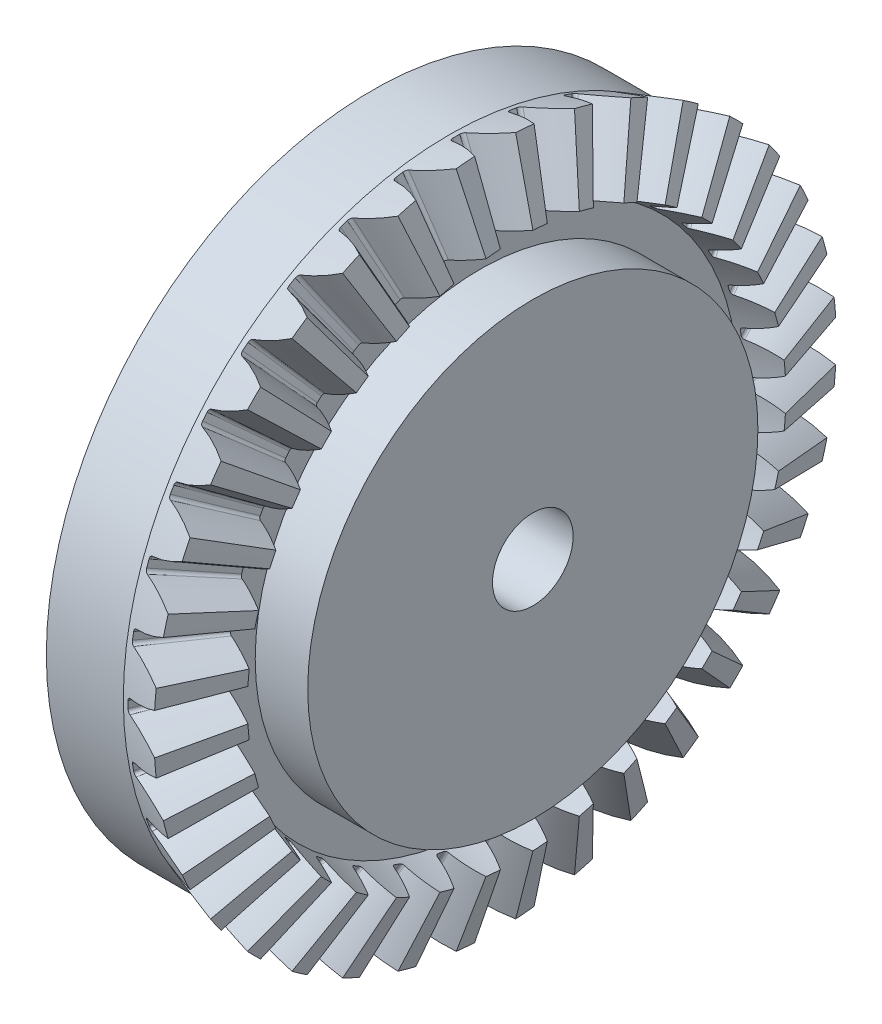
SolidWorks part; units mm, degrees
revolve "Base-Revolve" add sketch "BasProSke" angle 360 about L0
sketch "BasProSke" plane through (0, 0, 0) normal (0, 1, 0) x (1, 0, 0)
  line L0 (-10, 0) -> (60, 0) construction
  line L1 (0, 0) -> (0, 8.684)
  line L2 (0, 0) -> (0.8323, 0)
  line L3 (0.8323, 0) -> (0.8323, 6.8532)
  line L4 (3.948, 0) -> (-9.0794, 39.0823) construction
  line L5 (0, 8.684) -> (1.2284, 9.0935)
  line L6 (3.948, 0) -> (-23.6442, 92.2592) construction
  line L7 (3.948, 0) -> (0, 8.684) construction
  line L8 (1.2284, 9.0935) -> (1.8018, 7.1764)
  line L9 (1.8018, 7.1764) -> (0.8323, 6.8532)
  line L10 (0.948, 9) -> (-11.0363, 9) construction
  dimension "D1" = 17.368
  dimension "D2" = 3.948
  dimension "D3" = 9.4868
  dimension "D4" = 1.784
ref_plane "Plane1" through (0, 0, 0) normal (0, 0, 1) x (1, 0, 0)
ref_plane "Plane2" through (0, 0, 0) normal (0, 1, 0) x (1, 0, 0)
ref_plane "Plane3" through (0, 0, 0) normal (1, 0, 0) x (0, 0, -1)
other "Configuration Table"
sketch "HoldingSke" plane through (0, 0, 0) normal (0, 1, 0) x (1, 0, 0)
  line L0 (0, 0) -> (1.618, -1.1756)
  line L1 (-15, 0) -> (100, 0) construction
  line L2 (0, 0) -> (-122.6628, 25.2748)
  line L3 (0, 0) -> (-11.863, 4.5341)
  line L4 (0, 0) -> (6.9867, 5.0761)
  line L5 (0, 0) -> (-5.6217, -2.0967)
  line L6 (0, 0) -> (-10.5278, -7.1032)
  line L7 (-122.6628, 25.2748) -> (-122.6177, 31.2747)
  line L8 (-76.2, 0.5) -> (-75.9, 0.5)
  line L9 (-71.009, 38.7566) -> (-53.1078, 45.2721)
  line L10 (-76.2, 71.12) -> (104.1128, 71.12)
  line L11 (0, 0) -> (-2, 0)
  line L12 (-76.2, 101.6) -> (-76.181, 101.6)
  line L13 (24.9733, 27.94) -> (52.9546, 28.2287)
  line L14 (24.9733, 27.94) -> (24.9743, 27.94)
  line L15 (24.9733, 27.94) -> (100.3893, 30.0425)
  line L16 (-122.6628, 25.2748) -> (3.6233, -1.5681)
  circle A0 centre (0, 0) radius 1
  circle A1 centre (0, 0) radius 8.684
  circle A2 centre (0, 0) radius 10
  circle A3 centre (0, 0) radius 1
  dimension "Num_teeth" = 36
  dimension "Pitch_radius" = 180.3128
  dimension "Width" = 2
ref_plane "ToothPln" through (0.6142, 8.8887, 0) normal (-0.3162, 0.9487, 0) x (0, 0, -1)
ref_plane "ToothPln2" through (0.3948, -1.1844, 0) normal (-0.3162, 0.9487, 0) x (0, 0, 1)
sketch "TooCutSke" plane through (0.6142, 8.8887, 0) normal (-0.3162, 0.9487, 0) x (0, 0, -1)
  line L2 (0, 8.6481) -> (144.0891, -1638.2981) construction
  line L3 (0, 8.6481) -> (78.8921, -1755.5054) construction
  line L4 (0, -15.621) -> (0, 105.791) construction
  line L6 (-24.765, -0.6474) -> (21.082, -0.6474) construction
  line L7 (0.7844, -0.3176) -> (0.4017, -0.3347) construction
  arc A0 (-0.6442, -0.8114) -> (0.6442, -0.8114) centre (0, 8.6481) ccw
  arc A1 (-0.094, 0.4481) -> (0.094, 0.4481) centre (0, 8.6481) ccw
  circle A2 centre (0, 8.6481) radius 9 construction
  circle A3 centre (0, 8.6481) radius 8.4572 construction
  arc A4 (0.1883, 0.3711) -> (0.094, 0.4481) centre (0.0951, 0.3531) ccw
  arc A5 (0.1883, 0.3711) -> (0.6442, -0.8114) centre (3.7229, 1.0544) ccw
  arc A6 (-0.6442, -0.8114) -> (-0.1883, 0.3711) centre (-3.7229, 1.0544) ccw
  arc A7 (-0.094, 0.4481) -> (-0.1883, 0.3711) centre (-0.0951, 0.3531) ccw
  ellipse E0 centre (0, 2.2282) end of major axis (9.0935, 2.2282) minor radius 2.8756 construction
sketch "TooCutSke2" plane through (0.3948, -1.1844, 0) normal (-0.3162, 0.9487, 0) x (0, 0, 1)
  line L0 (0, 0) -> (0, 68.072) construction
  line L2 (21.082, 2.7461) -> (-20.32, 2.7461) construction
  circle A0 centre (0, 3.7454) radius 0.0127
  ellipse E1 centre (0, 0) end of major axis (-8.684, 0) minor radius 2.7461 construction
loft "ToothCut" cut profiles "TooCutSke2", "TooCutSke"
pattern_circular "TeethCuts" count 36 every 10 about axis through (-10, 0, 0) along (1, 0, 0) of "ToothCut"
sketch "草图1" plane through (0.8323, 0, 0) normal (1, 0, 0) x (0, 0, -1)
  circle A0 centre (0, 0) radius 6
  dimension "D1" = 12
extrude "凸台-拉伸1" add sketch "草图1" along normal blind 1.4
sketch "HubSke" plane through (0, 0, 0) normal (-1, 0, 0) x (0, 0, 1)
  circle A0 centre (0, 0) radius 8.684
  dimension "Diameter" = 17.368
extrude "Hub" add sketch "HubSke" along normal blind 2.0521
sketch "BorSke" plane through (0, 0, 0) normal (1, 0, 0) x (0, 0, -1)
  circle A0 centre (0, 0) radius 1.075
  dimension "Diameter" = 2.15
extrude "Bore" cut sketch "BorSke" along normal mid plane 12.0001
sketch "KeySke" plane through (0, 0, 0) normal (1, 0, 0) x (0, 0, -1)
  line L0 (-0.4, 0) -> (-0.4, 1.3)
  line L1 (-0.4, 1.3) -> (0.4, 1.3)
  line L2 (0.4, 1.3) -> (0.4, 0)
  line L3 (0, 0) -> (0, 34) construction
  line L4 (-0.4, 0) -> (0.4, 0)
  dimension "Offset" = 1.3
extrude "Keyway" [suppressed] cut sketch "KeySke" along normal mid plane 12.0001
pattern_circular "Keyway2" [suppressed] count 2 every 90 about axis through (-10, 0, 0) along (1, 0, 0)
equation "' \"Module@HoldingSke\" = 6.35"
equation "' \"Num_teeth@HoldingSke\" = 20"
equation "' \"Mating_teeth@HoldingSke\" = 12"
equation "' \"Ap@HoldingSke\" =  20"
equation "' \"Ap@HoldingSke\" = 20"
equation "' \"Width@HoldingSke\" = 0.5 * 25.4"
equation "' \"Hub_dia@HoldingSke\"= 2 * 25.4"
equation "' \"Hub_dia@HoldingSke\" = 2 * 25.4"
equation "' \"Mounting_dist@HoldingSke\" = 3 * 25.4"
equation "' \"Bore@HoldingSke\" = 19"
equation "' \"T_dim@HoldingSke\" = 0.1 * 25.4"
equation "' \"Width@KeySke\" = 0.25 * 25.4"
equation "' \"Show_teeth@HoldingSke\" = 100"
equation "' \"Backlash@HoldingSke\" = 0.009 * 25.4"
equation "' \"Addendum_fac@HoldingSke\" = 1.0"
equation "' \"Dedendum_fac@HoldingSke\" = 1.188"
equation "' \"Dedendum_add@HoldingSke\" = 0.002 * 25.4"
equation "' \"Clearance_fac@HoldingSke\" = 0.188"
equation "\"Pitch@HoldingSke\" = 1 / \"Module@HoldingSke\""
equation " \"Addendum_fac@HoldingSke\" = 0.54 + 0.46 / (\"Num_teeth@HoldingSke\" /  \"Mating_teeth@HoldingSke\" ) ^ 2"
equation "' \"Addendum_fac@HoldingSke\" = 2 - (0.54 + 0.46 / (\"Mating_teeth@HoldingSke\" /  \"Num_teeth@HoldingSke\" ) ^ 2)"
equation "\"Dedendum_fac@HoldingSke\" = 2.188 - \"Addendum_fac@HoldingSke\""
equation "\"Pitch_rad@BasProSke\" = \"Num_teeth@HoldingSke\" / \"Pitch@HoldingSke\" / 2"
equation "\"Pitch_ang@BasProSke\" = atn(\"Num_teeth@HoldingSke\" / \"Mating_teeth@HoldingSke\") * (180 / 3.14159265)"
equation "\"Addendum@BasProSke\" = \"Addendum_fac@HoldingSke\" / \"Pitch@HoldingSke\""
equation "\"Dedendum_plus@BasProSke\" = (\"Dedendum_fac@HoldingSke\" / \"Pitch@HoldingSke\" + \"Dedendum_add@HoldingSke\") * 1.25"
equation "\"Face_wid@BasProSke\" = \"Width@HoldingSke\""
equation "\"Radius@TooCutSke\" = ((\"Num_teeth@HoldingSke\" + 2 * \"Addendum_fac@HoldingSke\") / \"Pitch@HoldingSke\" ) / 2"
equation "\"Overcut_dia@TooCutSke\" =  1.02 * (\"Num_teeth@HoldingSke\" + 2 * \"Addendum_fac@HoldingSke\") / \"Pitch@HoldingSke\""
equation "\"Pitch_dia@TooCutSke\" = \"Num_teeth@HoldingSke\" / \"Pitch@HoldingSke\""
equation "\"Base_dia@TooCutSke\" = \"Num_teeth@HoldingSke\" / \"Pitch@HoldingSke\" * cos((\"Ap@HoldingSke\"  * 3.14159265 / 180))"
equation "'  \"Root_dia@TooCutSke\" =  (\"Num_teeth@HoldingSke\" + 2) / \"Pitch@HoldingSke\" - 2 * (\"Addendum_fac@HoldingSke\" + \"Dedendum_fac@HoldingSke\") / \"Pitch@HoldingSke\" - \"Dedendum_add@HoldingSke\" * 2"
equation "'  \"Root_dia@TooCutSke\" = (\"Num_teeth@HoldingSke\" + 2) / \"Pitch@HoldingSke\" - 2 * (\"Addendum_fac@HoldingSke\" + \"Dedendum_fac@HoldingSke\") / \"Pitch@HoldingSke\" - \"Dedendum_add@HoldingSke\" * 2"
equation "\"Root_dia@TooCutSke\" =  \"Num_teeth@HoldingSke\" / \"Pitch@HoldingSke\" -  2 * \"Dedendum_fac@HoldingSke\" / \"Pitch@HoldingSke\" - \"Dedendum_add@HoldingSke\" * 2"
equation "\"Half_ang@TooCutSke\" = 180 / \"Num_teeth@HoldingSke\""
equation "\"Half_CT@TooCutSke\" = \"Num_teeth@HoldingSke\" / \"Pitch@HoldingSke\" * sin((3.14159265 / 2 / \"Num_teeth@HoldingSke\")) / 2 - 2 * \"Backlash@HoldingSke\" / 4"
equation "\"Flank_rad@TooCutSke\" = \"Num_teeth@HoldingSke\" / \"Pitch@HoldingSke\" / 5"
equation "\"Root_fillet@TooCutSke\" = \"Clearance_fac@HoldingSke\" / \"Pitch@HoldingSke\" + \"Dedendum_add@HoldingSke\""
equation "\"Offset@ToothPln2\"  = \"Num_teeth@HoldingSke\" / \"Pitch@HoldingSke\" / 2 / sin(atn(\"Num_teeth@HoldingSke\" / \"Mating_teeth@HoldingSke\"))"
equation "\"Dedendum_plus@TooCutSke2\" = \"Dedendum_plus@BasProSke\""
equation "\"MHD@HoldingSke\" = \"Num_teeth@HoldingSke\" / \"Pitch@HoldingSke\" - 2 * \"Dedendum_plus@BasProSke\" * cos(atn(\"Num_teeth@HoldingSke\" / \"Mating_teeth@HoldingSke\"))"
equation "\"MBD@HoldingSke\" = \"Num_teeth@HoldingSke\" / \"Pitch@HoldingSke\" - 2 * \"Dedendum_plus@BasProSke\" * cos(atn(\"Num_teeth@HoldingSke\" / \"Mating_teeth@HoldingSke\")) - 0.002 * 25.4"
equation "\"MnMD@HoldingSke\" =  \"Num_teeth@HoldingSke\" / \"Pitch@HoldingSke\" / 2 / (\"Num_teeth@HoldingSke\" / \"Mating_teeth@HoldingSke\") + \"Dedendum_plus@BasProSke\" * sin(atn(\"Num_teeth@HoldingSke\" / \"Mating_teeth@HoldingSke\"))"
equation "\"OAL@HoldingSke\" = \"MnMD@HoldingSke\""
equation "\"MHD@HoldingSke\" = ((sgn( \"MHD@HoldingSke\" - \"Hub_dia@HoldingSke\" )-1)*( \"MHD@HoldingSke\" - \"Hub_dia@HoldingSke\" ))/-2+ \"Hub_dia@HoldingSke\""
equation "\"MBD@HoldingSke\" = ((sgn( \"MBD@HoldingSke\" - \"Bore@HoldingSke\" )-1)*( \"MBD@HoldingSke\" - \"Bore@HoldingSke\" ))/-2+ \"Bore@HoldingSke\""
equation "\"Face_wid@BasProSke\" = ((sgn( \"Face_wid@BasProSke\" - \"Offset@ToothPln2\" * 0.9)-1)*( \"Face_wid@BasProSke\" - \"Offset@ToothPln2\" * 0.9))/-2+ \"Offset@ToothPln2\" * 0.9"
equation "\"OAL@HoldingSke\" = ((sgn( \"OAL@HoldingSke\" - \"Mounting_dist@HoldingSke\" )+1)*( \"OAL@HoldingSke\" - \"Mounting_dist@HoldingSke\" ))/2 + \"Mounting_dist@HoldingSke\" + 0.000002 * 25.4"
equation "\"Num_teeth@TeethCuts\" = int( \"Show_teeth@HoldingSke\" ) + 1"
equation "\"Num_teeth@TeethCuts\" = ((sgn( \"Num_teeth@TeethCuts\" - \"Num_teeth@HoldingSke\" )-1)*( \"Num_teeth@TeethCuts\" - \"Num_teeth@HoldingSke\" ))/-2+ \"Num_teeth@HoldingSke\""
equation "\"Num_teeth@TeethCuts\" = ((sgn( \"Num_teeth@TeethCuts\" - 2.0)+1)*( \"Num_teeth@TeethCuts\" - 2.0))/2 +2.0"
equation "\"Angle@TeethCuts\" = 360.0 / \"Num_teeth@HoldingSke\""
equation "\"Diameter@HubSke\" = \"MHD@HoldingSke\""
equation "\"Length@Hub\" = \"OAL@HoldingSke\" - \"MnMD@HoldingSke\" + 0.000002 * 25.4"
equation "\"D1@Bore\" = \"OAL@HoldingSke\" * 2.0"
equation "\"D1@Keyway\" = \"OAL@HoldingSke\" * 2.0"
equation "\"Offset@KeySke\" = \"T_dim@HoldingSke\" + \"MBD@HoldingSke\" / 2.0"
